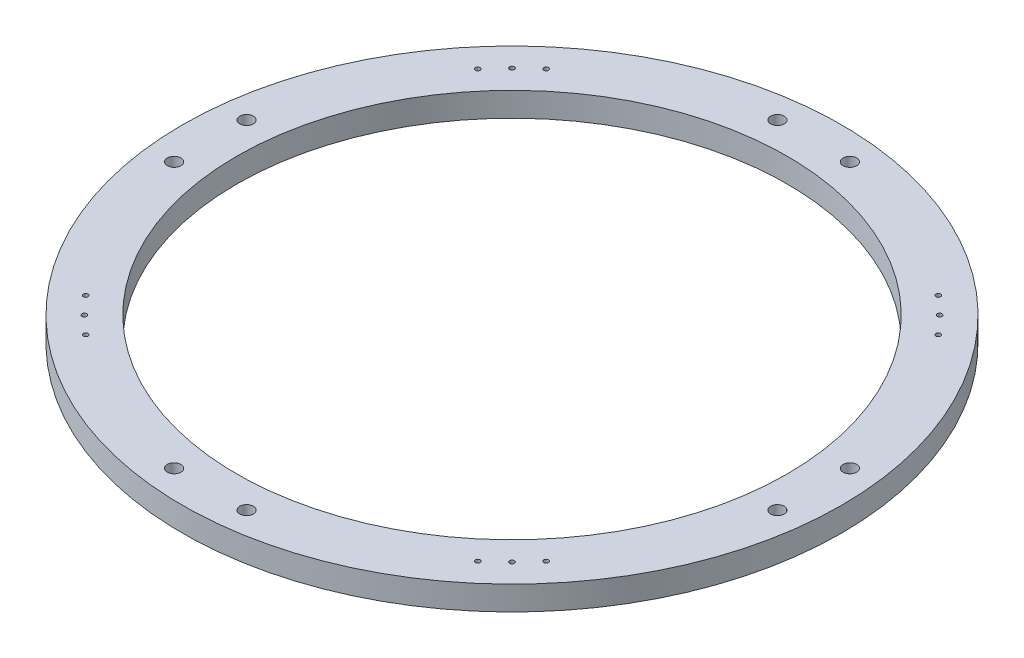
SolidWorks part; units mm, degrees
material "Oak"
ref_plane "Front Plane" through (0, 0, 0) normal (0, 0, 1) x (1, 0, 0)
ref_plane "Top Plane" through (0, 0, 0) normal (0, 1, 0) x (1, 0, 0)
ref_plane "Right Plane" through (0, 0, 0) normal (1, 0, 0) x (0, 0, -1)
sketch "Sketch1" plane through (0, 0, 0) normal (0, 0, 1) x (1, 0, 0)
  line L0 (0, -200000) -> (0, 218797.9879) construction
  line L5 (0, -200000) -> (0, 218797.9879) construction
  line L6 (173.3622, 191.5688) -> (173.3622, 178.8688)
  line L7 (144.7872, 191.5688) -> (173.3622, 191.5688)
  line L8 (173.3622, 178.8688) -> (144.7872, 178.8688)
  line L9 (144.7872, 178.8688) -> (144.7872, 191.5688)
revolve "Revolve1" add sketch "Sketch1" angle 360 about L5
hole_wizard "Tap Drill for M3x0.5 Tap1" positions "Sketch5" profile "Sketch6" hole size "M3x0.5" standard "ANSI Metric" end condition through all
sketch "Sketch5" plane through (0, 191.5688, 0) normal (0, 1, 0) x (1, 0, 0)
  line L0 (0, 0) -> (-112.4828, 112.4828) construction
  point P0 (-112.4828, 112.4828)
  point P3 (-103.1435, 121.104)
  point P6 (-121.104, 103.1435)
  dimension "D1" = 159.0747
sketch "Sketch6" plane through (-112.4828, 191.5688, -112.4828) normal (1, 0, 0) x (0, 0, 1)
  line L0 (0, 0) -> (0, 12.7)
  line L1 (0, 12.7) -> (1.25, 12.7)
  line L2 (1.25, 12.7) -> (1.25, 0)
  line L5 (1.25, 0) -> (0, 0)
  line L11 (0, -6.35) -> (0, 107.95) construction
  dimension "Thru Hole Dia." = 2.5
  dimension "Thru Hole Depth" = 12.7
sketch "Sketch7" plane through (0, 191.5688, 0) normal (0, 1, 0) x (1, 0, 0)
  line L0 (0, 0) -> (158.6742, 0) construction
  line L1 (158.6742, 19.05) -> (158.6742, -19.05) construction
  line L2 (158.6742, -19.05) -> (0, 0) construction
  line L3 (0, 0) -> (158.6742, 19.05) construction
  circle A0 centre (158.6742, -19.05) radius 3.5719
  circle A1 centre (158.6742, 19.05) radius 3.5719
  point P6 (158.6742, 0)
  dimension "D3" = 7.1437
  dimension "D1" = 38.1
  dimension "D2" = 159.8137
extrude "Cut-Extrude1" cut sketch "Sketch7" against normal through all
pattern_circular "CirPattern1" count 4 over 360 about axis through (0, -200000, 0) along (0, -1, 0) of "Tap Drill for M3x0.5 Tap1", "Cut-Extrude1"
